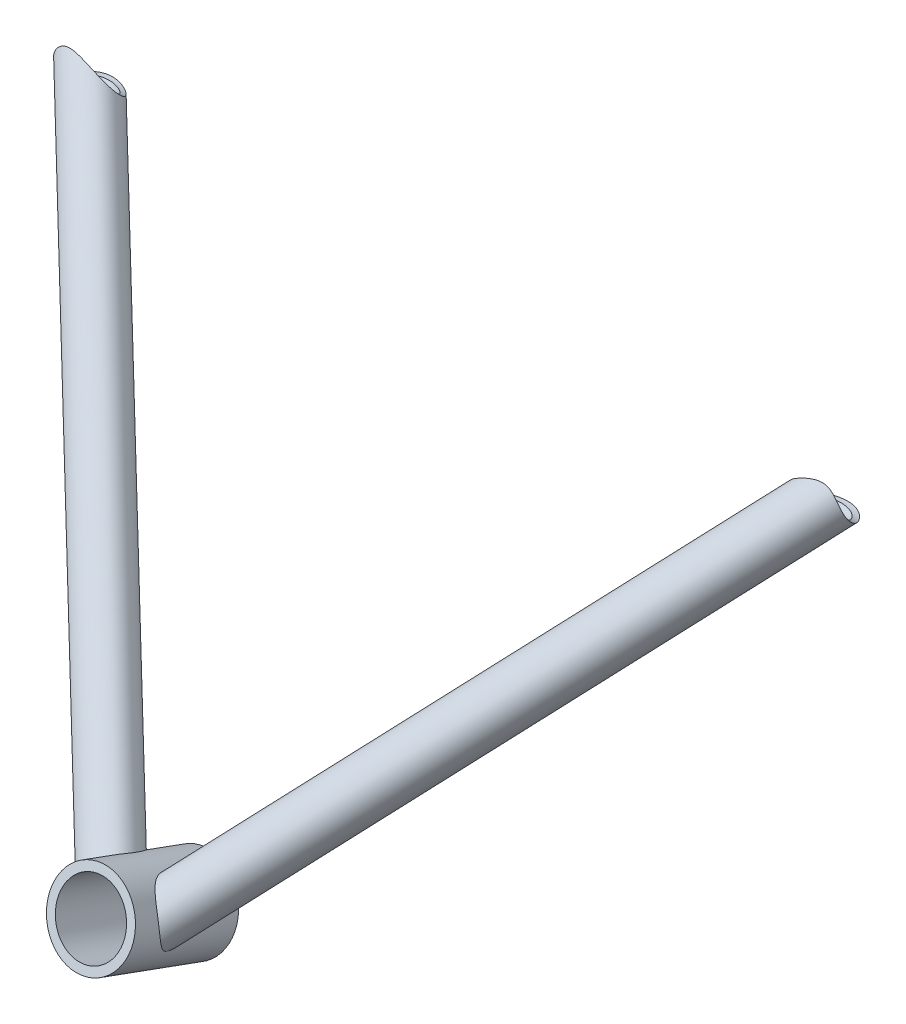
SolidWorks part; units mm, degrees
material "AISI 4130 Steel, normalized at 870C"
ref_plane "Front Plane" through (0, 0, 0) normal (0, 0, 1) x (1, 0, 0)
ref_plane "Top Plane" through (0, 0, 0) normal (0, 1, 0) x (1, 0, 0)
ref_plane "Right Plane" through (0, 0, 0) normal (1, 0, 0) x (0, 0, -1)
sketch "Sketch3" plane through (0, 0, 0) normal (0, 1, 0) x (1, 0, 0)
  line L0 (-5.08, -6.35) -> (5.08, -6.35) construction
  line L2 (0, -88.2205) -> (0, 88.2205) construction
  line L3 (5.08, 0) -> (-5.08, 0) construction
  dimension "D1" = 5.08
  dimension "D2" = 10.16
  dimension "D3" = 6.35
  dimension "D4" = 10.16
  dimension "D5" = 5.08
ref_plane "Plane1" through (0, 3.1441, 3.6169) normal (0, 0.6561, 0.7547) x (1, 0, 0)
ref_plane "Plane3" through (0, 0, 0) normal (0, 0.342, 0.9397) x (-1, 0, 0)
sketch "Sketch1" plane through (0, 0, 0) normal (0, 0.342, 0.9397) x (1, 0, 0)
  circle A0 centre (0, 0) radius 15.875
  dimension "D1" = 31.75
extrude "Boss-Extrude1" add sketch "Sketch1" along normal mid plane 41.402 contours A0
sketch "Sketch4" plane through (0, 3.1441, 3.6169) normal (0, 0.6561, 0.7547) x (1, 0, 0)
  line L0 (-5.08, -4.166) -> (-143.484, 193.4954)
  line L2 (0, -90.5202) -> (0, 90.5202) construction
  dimension "D2" = 35
  dimension "D3" = 241.3
sweep "Sweep1" add path "Sketch4" circular profile diameter 19.05 parameters "D3"=19.05
sketch "Sketch15" plane through (0, 3.1441, 3.6169) normal (0, 0.6561, 0.7547) x (1, 0, 0)
  line L0 (5.08, -4.166) -> (143.484, 193.4954)
  line L1 (0, -90.5202) -> (0, 90.5202) construction
  dimension "D1" = 241.3
  dimension "D2" = 35
sweep "Sweep2" add path "Sketch15" circular profile diameter 19.05 parameters "D3"=19.05
sketch "Sketch36" plane through (-138.1179, 148.8686, -129.4095) normal (-0.5736, 0.6182, -0.5374) x (0.8191, 0.4394, -0.3687)
  circle A0 centre (-6.5024, -4.8578) radius 7.9375
  dimension "D1" = 15.875
extrude "Cut-Extrude2" cut sketch "Sketch36" against normal up to surface (251.5099 mm away) up to face at (15.2328, -2.8486, 5.2417)
sketch "Sketch37" plane through (138.1179, 148.8686, -129.4095) normal (0.5736, 0.6182, -0.5374) x (0.8191, -0.4394, 0.3687)
  circle A0 centre (6.5024, -4.8578) radius 7.9375
  dimension "D1" = 15.875
extrude "Cut-Extrude3" cut sketch "Sketch37" against normal up to surface (226.8376 mm away) up to face at (10.6472, -5.7729, 18.5671)
sketch "Sketch77" plane through (0, 7.0802, 19.4526) normal (0, 0.342, 0.9397) x (1, 0, 0)
  circle A1 centre (0, 0) radius 15.875
extrude "Boss-Extrude2" add sketch "Sketch77" against normal up to surface (41.402 mm away) up to face at (0, -21.9978, -14.023)
sketch "Sketch2" plane through (0, -7.0802, -19.4526) normal (0, -0.342, -0.9397) x (-1, 0, 0)
  circle A0 centre (0, 0) radius 12.7
  dimension "D1" = 25.4
extrude "Cut-Extrude1" cut sketch "Sketch2" against normal up to next
ref_plane "Plane2" through (0, 0, -127) normal (0, 0, 1) x (1, 0, 0)
sketch "Sketch40" plane through (-106.934, 0, -127) normal (0, 0, 1) x (1, 0, 0)
  line L2 (106.934, -85.9333) -> (106.934, 85.9333) construction
  line L3 (100.2024, 162.3048) -> (-63.6638, 149.8608)
  line L4 (113.6656, 162.3048) -> (277.5318, 149.8608)
  arc A0 (100.2024, 162.3048) -> (113.6656, 162.3048) centre (106.934, 73.66) cw
  point P0 (106.934, 162.56)
  point P7 (106.934, 162.56)
  dimension "D1" = 164.338
  dimension "D3" = 88.9
  dimension "D2" = 164.338
  dimension "D4" = 4.75
ref_plane "Plane4" through (170.5978, 149.8608, -127) normal (-0.9971, 0.0757, 0) x (0, 0, 1)
sketch "Sketch83" plane through (170.5978, 149.8608, -127) normal (-0.9971, 0.0757, 0) x (0, 0, 1)
  circle A0 centre (0, -0.2552) radius 12.7
  dimension "D1" = 25.4
sweep "Cut-Sweep1" cut profiles "Sketch83" path "Sketch40"
ref_axis "Axis1" through (-73.2968, -84.4775, 79.7851) along (0.5736, 0.6182, -0.5374)
ref_axis "Axis2" through (57.6633, -67.627, 65.1373) along (-0.5736, 0.6182, -0.5374)
